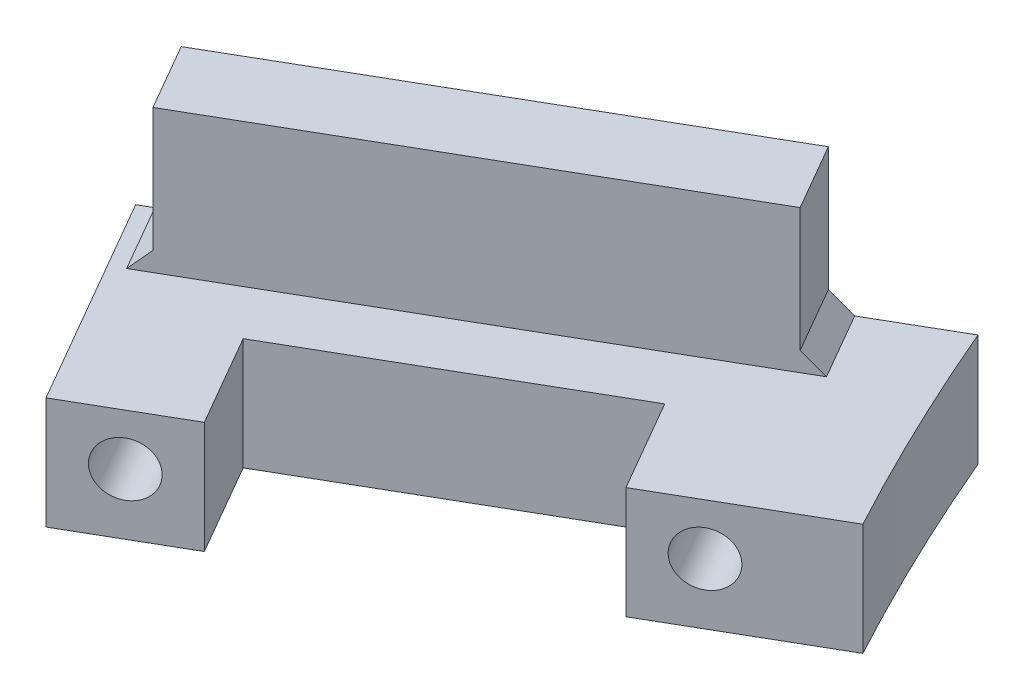
SolidWorks part; units mm, degrees
ref_plane "Front Plane" through (0, 0, 0) normal (0, 0, 1) x (1, 0, 0)
ref_plane "Top Plane" through (0, 0, 0) normal (0, 1, 0) x (1, 0, 0)
ref_plane "Right Plane" through (0, 0, 0) normal (1, 0, 0) x (0, 0, -1)
sketch "Sketch1" plane through (0, 0, 0) normal (-0.5, 0, -0.866) x (-0.866, 0, 0.5)
  line L0 (-3.3544, 1.65) -> (-3.3544, 0)
  line L1 (-11.3544, 1.65) -> (-11.3544, 0)
  line L3 (1.5356, 3.15) -> (-16.2444, 3.15)
  line L4 (1.5356, 2.9) -> (-16.2444, 2.9)
  line L6 (-0.9644, 5.29) -> (-0.9644, 3.55)
  line L8 (-13.7444, 3.55) -> (-13.7444, 5.29)
  line L14 (-3.6044, 3.15) -> (-3.6044, 1.65)
  line L15 (-11.1044, 1.65) -> (-11.1044, 3.15)
  line L16 (-3.3544, 3.15) -> (-3.3544, 1.65)
  line L17 (-11.3544, 1.65) -> (-11.3544, 3.15)
  line L24 (-4.1294, 2.9622) -> (-4.1294, 0)
  line L25 (-4.1294, 0) -> (0, 0)
  line L26 (0, 0) -> (0, 7.9)
  line L27 (0, 7.9) -> (-16, 7.9)
  line L28 (-16, 7.9) -> (-16, 0)
  line L29 (-16, 0) -> (-10.5794, 0)
  line L30 (-10.5794, 0) -> (-10.5794, 2.9622)
  line L31 (-10.5794, 2.9622) -> (-8.8794, 2.9622)
  line L32 (-8.8794, 2.9622) -> (-8.8794, 0)
  line L33 (-8.8794, 0) -> (-5.8294, 0)
  line L34 (-5.8294, 0) -> (-5.8294, 2.9622)
  line L35 (-5.8294, 2.9622) -> (-4.1294, 2.9622)
  circle A1 centre (-1.8544, 1.575) radius 0.7
  circle A3 centre (-12.8544, 1.575) radius 0.7
  dimension "D1" = 0.25
  dimension "D2" = 0.25
extrude "Boss-Extrude1" add sketch "Sketch1" along normal offset from surface (4.348 mm away) 0.25 contours L28 L29 L1 L17 L4 A3 | L25 L26 L4 L16 L0 A1 region at (2.8666, 2.275, -1.655) region at (11.9367, 1.4339, -6.8917) offset beyond the face yes
sketch "Sketch3" plane through (-2.174, 0, -3.7655) normal (-0.5, 0, -0.866) x (-0.866, 0, 0.5)
  line L1 (-11.3544, 2.9) -> (-3.3544, 2.9)
  line L2 (-11.3544, 2.9) -> (-11.3544, 0)
  line L3 (-11.3544, 0) -> (-3.3544, 0)
  line L4 (-3.3544, 2.9) -> (-3.3544, 0)
  line L5 (-3.3544, 0) -> (0, 0)
  line L6 (0, 0) -> (0, 2.9)
  line L7 (0, 2.9) -> (-3.3544, 2.9)
  line L8 (-3.3544, 2.9) -> (-3.3544, 0)
  line L9 (-3.3544, 0) -> (0, 0)
  line L10 (0, 0) -> (0, 2.9)
  line L11 (0, 2.9) -> (-3.3544, 2.9)
  line L12 (-11.3544, 2.9) -> (-16, 2.9)
  line L13 (-16, 2.9) -> (-16, 0)
  line L14 (-16, 0) -> (-11.3544, 0)
  line L15 (-11.3544, 0) -> (-11.3544, 2.9)
  line L16 (-11.3544, 2.9) -> (-16, 2.9)
  line L17 (-16, 2.9) -> (-16, 0)
  line L18 (-16, 0) -> (-11.3544, 0)
  line L19 (-11.3544, 0) -> (-11.3544, 2.9)
  line L20 (-3.3544, 2.9) -> (-3.3544, 0)
  line M10 (-3.3544, 2.9) -> (-3.3544, 0)
  dimension "D1" = 0
  dimension "D2" = 0
extrude "Boss-Extrude2" add sketch "Sketch3" against normal offset from surface (1.598 mm away) 0.25 contours L2 L3 L1 M10 region at (4.1951, 1.45, -7.4427)
sketch "Sketch4" plane through (-2.174, 0, -3.7655) normal (-0.5, 0, -0.866) x (-0.866, 0, 0.5)
  line L1 (-0.9644, 5.29) -> (-0.9644, 3.55)
  line L3 (-13.7444, 3.55) -> (-13.7444, 5.29)
  line L5 (-8.5331, 6.8572) -> (-6.1835, 6.8572)
  line L6 (-1.2144, 5.29) -> (-1.2144, 3.55)
  line L7 (-13.4944, 3.55) -> (-13.4944, 5.29)
  line L8 (-8.5331, 6.6072) -> (-6.1835, 6.6072)
  line L9 (-13.4944, 6.6072) -> (-1.2144, 6.6072)
  line L10 (-13.4944, 5.29) -> (-8.5331, 5.29)
  line L11 (-13.4944, 5.29) -> (-13.4944, 6.6072)
  line L12 (-13.4944, 6.6072) -> (-8.5331, 6.6072)
  line L13 (-8.5331, 5.29) -> (-8.5331, 6.6072)
  line L14 (-6.1835, 6.6072) -> (-1.2144, 6.6072)
  line L15 (-6.1835, 6.6072) -> (-6.1835, 5.29)
  line L16 (-6.1835, 5.29) -> (-1.2144, 5.29)
  line L17 (-1.2144, 6.6072) -> (-1.2144, 5.29)
  line L18 (-13.4944, 6.6072) -> (-13.4944, 2.8455)
  line L19 (-1.2144, 6.6072) -> (-1.2144, 2.8455)
  line L20 (-13.4944, 2.8455) -> (-1.2144, 2.8455)
  line L21 (0, 2.9) -> (-16, 2.9)
  line L22 (-16, 2.9) -> (-16, 0)
  line L23 (-16, 0) -> (0, 0)
  line L24 (0, 0) -> (0, 2.9)
  line L25 (0, 2.9) -> (-16, 2.9)
  line L26 (-16, 2.9) -> (-16, 0)
  line L27 (-16, 0) -> (0, 0)
  line L28 (0, 0) -> (0, 2.9)
  circle M9 centre (-12.8544, 1.575) radius 0.7
  line M10 (0, 2.9) -> (-16, 2.9)
  line M11 (-16, 2.9) -> (-16, 0)
  line M12 (-16, 0) -> (0, 0)
  line M13 (0, 0) -> (0, 2.9)
  circle M14 centre (-1.8544, 1.575) radius 0.7
  dimension "D1" = 0.25
  dimension "D2" = 0
extrude "Boss-Extrude3" add sketch "Sketch4" along normal blind 2 contours L17 L9 L15 L16 | L10 L13 L9 L11 | L19 L6 L16 L15 L8 L13 L10 L7 L18 M10 | L20 L18 L19 M10 M11 M12 M13 M14 M9 | M9 | M14 | L9 L18 L20 L19 region at (4.1954, 4.2718, -7.4429) region at (1.0294, 5.9486, -5.615) region at (4.8033, 1.4187, -7.7938) region at (7.3642, 5.9486, -9.2724) region at (8.9582, 1.575, -10.1927) region at (-0.568, 1.575, -4.6927)
other "Move Face1" flip direction yes face at (-1.587, 1.45, -2.7488) offset 0.35 parameters "D1"=0.35
chamfer "Chamfer1" distance 0.5 angle 45 2 edges at (9.0125, 2.9, -11.3787) (-1.6223, 2.9, -5.2387)
sketch "Sketch5" plane through (0, 0, 0) normal (0, -1, 0) x (1, 0, 0)
  line L0 (10.6824, -13.4975) -> (11.1021, -13.7399)
  line L8 (0.3031, -0.175) -> (-2.8709, -5.6725)
  line L9 (-2.8709, -5.6725) -> (10.6824, -13.4975)
  line L10 (10.6824, -13.4975) -> (13.8564, -8)
  line L11 (13.8564, -8) -> (9.8332, -5.6772)
  line L12 (9.8332, -5.6772) -> (8.4582, -8.0588)
  line L13 (8.4582, -8.0588) -> (1.53, -4.0588)
  line L14 (1.53, -4.0588) -> (2.905, -1.6772)
  line L15 (2.905, -1.6772) -> (0.3031, -0.175)
  line L16 (0.3031, -0.175) -> (-2.8709, -5.6725)
  line L18 (10.6824, -13.4975) -> (13.8564, -8)
  line L20 (9.8332, -5.6772) -> (8.4582, -8.0588)
  line L21 (8.4582, -8.0588) -> (1.53, -4.0588)
  line L22 (1.53, -4.0588) -> (2.905, -1.6772)
  line L23 (2.905, -1.6772) -> (0.3031, -0.175)
  arc A1 (13.8564, -8) -> (11.1021, -13.7399) centre (73.7553, -40.2732) ccw
  line M11 (10.6824, -13.4975) -> (13.8564, -8)
  dimension "D1" = 0
extrude "Boss-Extrude4" add sketch "Sketch5" against normal up to surface (2.9 mm away) contours A1 L0 M11 region at (11.7323, 0, -11.9758) up to face at (4.9565, 2.9, -6.671)
other "Move Face2" flip direction yes face at (12.4457, 1.45, -10.8538) offset 0.15 parameters "D1"=0.15
